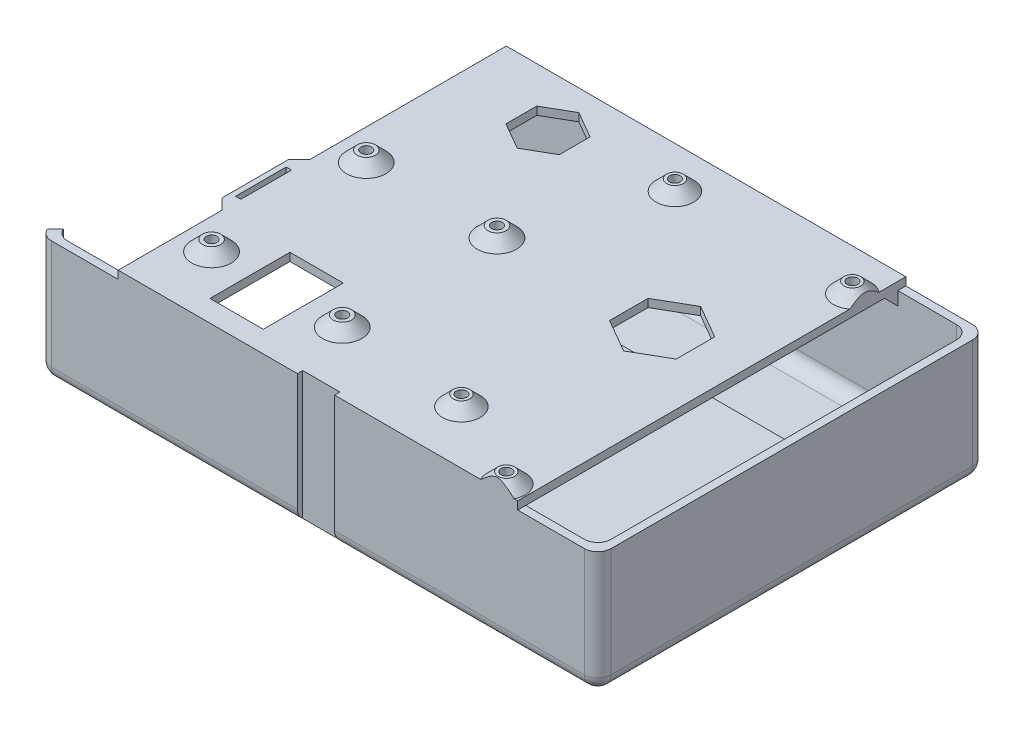
SolidWorks part; units mm, degrees
ref_plane "Front Plane" through (0, 0, 0) normal (0, 0, 1) x (1, 0, 0)
ref_plane "Top Plane" through (0, 0, 0) normal (0, 1, 0) x (1, 0, 0)
ref_plane "Right Plane" through (0, 0, 0) normal (1, 0, 0) x (0, 0, -1)
sketch "Sketch1" plane through (0, 0, 0) normal (0, 1, 0) x (1, 0, 0)
  line L1 (103.0685, -102.5392) -> (-106.7013, -102.5392)
  line L2 (103.0685, -102.5392) -> (103.0685, 42.9596)
  line L3 (103.0685, 42.9596) -> (-106.7013, 42.9596)
  line L4 (-106.7013, -102.5392) -> (-106.7013, 42.9596)
  line L6 (3.4026, -104.0392) -> (-8.5354, -104.0392) construction
  line L7 (-108.2013, -100.8421) -> (-108.2013, 38.9914) construction
  point P0 (0, 0)
  dimension "D1" = 1.5
  dimension "D2" = 1.5
extrude "Boss-Extrude1" add sketch "Sketch1" along normal blind 3
sketch "Sketch2" plane through (0, 3, 0) normal (0, 1, 0) x (1, 0, 0)
  line L4 (-106.7013, 42.9596) -> (-106.7013, -102.5392)
  line L5 (-106.7013, -102.5392) -> (103.0685, -102.5392)
  line L6 (103.0685, -102.5392) -> (103.0685, 42.9596)
  line L7 (103.0685, 42.9596) -> (-106.7013, 42.9596)
  line L8 (-106.7013, 42.9596) -> (-106.7013, -102.5392)
  line L9 (-106.7013, -102.5392) -> (103.0685, -102.5392)
  line L10 (103.0685, -102.5392) -> (103.0685, 42.9596)
  line L11 (103.0685, 42.9596) -> (-106.7013, 42.9596)
  line L16 (-103.7013, 39.9596) -> (-103.7013, -99.5392)
  line L17 (-103.7013, -99.5392) -> (100.0685, -99.5392)
  line L18 (100.0685, -99.5392) -> (100.0685, 39.9596)
  line L19 (100.0685, 39.9596) -> (-103.7013, 39.9596)
  line L20 (-103.7013, 39.9596) -> (-103.7013, -99.5392)
  line L21 (-103.7013, -99.5392) -> (100.0685, -99.5392)
  line L22 (100.0685, -99.5392) -> (100.0685, 39.9596)
  line L23 (100.0685, 39.9596) -> (-103.7013, 39.9596)
  dimension "D1" = 0
  dimension "D2" = 3
extrude "Boss-Extrude2" add sketch "Sketch2" along normal offset from surface (43 mm away) 20 offset beyond the face yes
sketch "Sketch3" plane through (-103.7013, 0, 0) normal (1, 0, 0) x (0, 0, -1)
  line L0 (39.9596, 46) -> (-99.5392, 46) construction
  line L1 (34.2109, 46) -> (-94.2682, 46)
  line L2 (34.2109, 46) -> (34.2109, 3)
  line L3 (34.2109, 3) -> (-94.2682, 3)
  line L4 (-94.2682, 46) -> (-94.2682, 3)
  line L5 (39.9596, 3) -> (-99.5392, 3) construction
extrude "Cut-Extrude1" cut sketch "Sketch3" against normal up to next
fillet "Fillet1" radius 5 8 edges at (100.0685, 24.5, 99.5392) (100.0685, 24.5, -39.9596) (-103.7013, 24.5, -39.9596) (-103.7013, 24.5, 99.5392) (103.0685, 23, -42.9596) (-106.7013, 23, -42.9596) (103.0685, 23, 102.5392) (-106.7013, 23, 102.5392)
fillet "Fillet2" radius 5 17 edges at (-103.7013, 3, 94.4037) (-102.2369, 3, 98.0748) (-1.8164, 3, 99.5392) (98.604, 3, 98.0748) (100.0685, 3, 29.7898) (98.604, 3, -38.4951) (-103.7013, 3, -34.5852) (-102.2369, 3, -38.4951) (-105.2369, 0, 101.0748) (-106.7013, 0, 29.7898) (-105.2369, 0, -41.4951) (-1.8164, 0, -42.9596) (101.604, 0, -41.4951) (103.0685, 0, 29.7898) (101.604, 0, 101.0748) (-1.8164, 3, -39.9596) (-1.8164, 0, 102.5392)
sketch "Sketch4" plane through (0, 46, 0) normal (0, 1, 0) x (1, 0, 0)
  line L0 (-101.7013, -102.5392) -> (98.0685, -102.5392) construction
  line L1 (-76.7013, -102.5392) -> (73.0685, -102.5392)
  line L2 (-76.7013, -102.5392) -> (-76.7013, 42.9596)
  line L3 (-76.7013, 42.9596) -> (73.0685, 42.9596)
  line L4 (73.0685, -102.5392) -> (73.0685, 42.9596)
  line L6 (98.0685, 42.9596) -> (-101.7013, 42.9596) construction
  line L7 (103.0685, -97.5392) -> (103.0685, 37.9596) construction
  line L8 (-106.7013, -94.2682) -> (-106.7013, -97.5392) construction
  dimension "D1" = 30
  dimension "D2" = 30
extrude "Boss-Extrude3" add sketch "Sketch4" along normal blind 3
sketch "Sketch6" plane through (0, 49, 0) normal (0, 1, 0) x (1, 0, 0)
  circle A0 centre (-16.2013, -79.0392) radius 1.4 construction
  circle A1 centre (-65.2013, -79.0392) radius 1.4 construction
  circle A2 centre (-16.2013, -21.0392) radius 1.4 construction
  circle A3 centre (-65.2013, -21.0392) radius 1.4 construction
  circle A4 centre (-16.2013, -79.0392) radius 1.4 construction
  circle A5 centre (-65.2013, -79.0392) radius 1.4 construction
  circle A6 centre (-16.2013, -21.0392) radius 1.4 construction
  circle A7 centre (-65.2013, -21.0392) radius 1.4 construction
  circle A8 centre (-65.2013, -21.0392) radius 3.4
  circle A9 centre (-65.2013, -79.0392) radius 3.4
  circle A10 centre (-16.2013, -21.0392) radius 3.4
  circle A11 centre (-16.2013, -79.0392) radius 3.4
  circle A12 centre (-65.2013, -21.0392) radius 1.1
  circle A13 centre (-16.2013, -21.0392) radius 1.1
  circle A14 centre (-65.2013, -79.0392) radius 1.1
  circle A15 centre (-16.2013, -79.0392) radius 1.1
  dimension "D2" = 2.2
  dimension "D3" = 2.2
  dimension "D4" = 2.2
  dimension "D5" = 2.2
  dimension "D1" = 2
extrude "Boss-Extrude4" add sketch "Sketch6" along normal up to surface (4 mm away)
sketch "Sketch7" plane through (0, 0, 0) normal (0, 1, 0) x (1, 0, 0)
  line L0 (-109.4507, 42.9596) -> (-106.8257, 40.3346)
  line L5 (-66.7013, 0.2102) -> (-66.7013, -59.7898)
  line L6 (-66.7013, -59.7898) -> (-99.0763, -92.1648)
  line L7 (-109.4507, -102.5392) -> (-109.4507, 42.9596)
  line L8 (-76.7013, 42.9596) -> (-76.7013, -102.5392) construction
  line L9 (-66.7013, -59.7898) -> (-66.7013, -102.5392) construction
  line L10 (-66.7013, -102.5392) -> (-109.4507, -102.5392) construction
  line L11 (-98.8263, 32.3352) -> (-66.7013, 0.2102)
  line L12 (-66.7013, 0.2102) -> (-66.7013, 42.9596) construction
  line L13 (-66.7013, 42.9596) -> (-109.4507, 42.9596) construction
  line L14 (-106.8257, 40.3346) -> (-98.8263, 32.3352)
  line L15 (-76.7013, 42.9596) -> (-101.7013, 42.9596) construction
  line L16 (-101.7013, -102.5392) -> (-76.7013, -102.5392) construction
  line L22 (-99.0763, -92.1648) -> (-107.0757, -100.1642)
  line L23 (-107.0757, -100.1642) -> (-109.4507, -102.5392)
  dimension "D1" = 45
  dimension "D2" = 45
  dimension "D3" = 10
  dimension "D4" = 60
sketch "Sketch8" plane through (0, 49, 0) normal (0, 1, 0) x (1, 0, 0)
  circle A0 centre (68.5185, 27.4596) radius 1.95 construction
  circle A1 centre (2.0185, 27.4596) radius 1.95 construction
  circle A2 centre (68.5185, 27.4596) radius 1.95 construction
  circle A3 centre (2.0185, 27.4596) radius 1.95 construction
  circle A4 centre (2.0185, 27.4596) radius 1.1
  circle A5 centre (68.5185, 27.4596) radius 1.1
  circle A6 centre (2.0185, 27.4596) radius 3.1
  circle A7 centre (68.5185, 27.4596) radius 3.1
  dimension "D1" = 2.2
  dimension "D2" = 2.2
  dimension "D3" = 2
extrude "Boss-Extrude5" add sketch "Sketch8" along normal up to surface (4 mm away)
sketch "Sketch9" plane through (0, 49, 0) normal (0, 1, 0) x (1, 0, 0)
  circle A0 centre (31.8985, -82.4792) radius 1.5 construction
  circle A1 centre (65.4585, -99.1992) radius 1.5 construction
  circle A2 centre (31.8985, -82.4792) radius 1.5 construction
  circle A3 centre (65.4585, -99.1992) radius 1.5 construction
  circle A4 centre (31.8985, -82.4792) radius 1.1
  circle A5 centre (65.4585, -99.1992) radius 1.1
  circle A6 centre (31.8985, -82.4792) radius 3.1
  circle A7 centre (65.4585, -99.1992) radius 3.1
  dimension "D1" = 2.2
  dimension "D2" = 2.2
  dimension "D3" = 2
  dimension "D4" = 2
extrude "Boss-Extrude6" add sketch "Sketch9" along normal up to surface (4 mm away) contours A7 A5 | A6 A4 region at (28.8862, 49, 82.4792) region at (62.4462, 49, 99.1992)
extrude "Cut-Extrude3" cut sketch "Sketch7" along normal up to surface (46 mm away) up to face at (-1.8164, 46, 29.7898)
extrude "Cut-Extrude4" cut sketch "Sketch6<3>" against normal up to next contours A14 | A12 | A13 | A15 region at (-65.2013, 49, 21.0392) region at (-16.2013, 49, 21.0392) region at (-65.2013, 49, 79.0392) region at (-16.2013, 49, 79.0392)
sketch "Sketch6<3>" plane through (0, 49, 0) normal (0, 1, 0) x (1, 0, 0) same geometry as "Sketch6"
extrude "Cut-Extrude5" cut sketch "Sketch8<2>" against normal up to next contours A4 | A5 region at (2.0185, 49, -27.4596) region at (68.5185, 49, -27.4596)
sketch "Sketch8<2>" plane through (0, 49, 0) normal (0, 1, 0) x (1, 0, 0) same geometry as "Sketch8"
extrude "Cut-Extrude6" cut sketch "Sketch9<2>" against normal up to surface (3 mm away) contours A4 | A5 region at (31.8985, 49, 82.4792) region at (65.4585, 49, 99.1992) up to face at (2.0185, 46, -28.5596)
sketch "Sketch9<2>" plane through (0, 49, 0) normal (0, 1, 0) x (1, 0, 0) same geometry as "Sketch9"
chamfer "Chamfer1" distance 4 angle 45 8 edges at (-65.2013, 49, 17.6392) (-65.2013, 49, 75.6392) (-16.2013, 49, 17.6392) (-16.2013, 49, 75.6392) (65.4585, 49, 96.0992) (31.8985, 49, 79.3792) (68.5185, 49, -30.5596) (2.0185, 49, -30.5596)
sketch "Sketch10" plane through (0, 0, 0) normal (0, 1, 0) x (1, 0, 0)
  line L0 (-9.5354, -102.5392) -> (-9.5354, -100.5392)
  line L1 (-76.7013, -102.5392) -> (59.1932, -102.5392) construction
  line L2 (-9.5354, -100.5392) -> (4.4026, -100.5392)
  line L3 (4.4026, -100.5392) -> (4.4026, -102.5392)
  line L4 (4.4026, -102.5392) -> (-9.5354, -102.5392)
  line L5 (-8.5354, -104.0392) -> (-8.5354, -105.7188) construction
  dimension "D1" = 1
  dimension "D2" = 1
  dimension "D3" = 2
extrude "Cut-Extrude7" cut sketch "Sketch10" along normal up to surface (49 mm away) up to face at (-65.2013, 49, 13.6392)
sketch "Sketch11" plane through (0, 49, 0) normal (0, 1, 0) x (1, 0, 0)
  line L0 (-76.7013, -35.5392) -> (-80.7013, -35.5392)
  line L1 (-76.7013, 42.9596) -> (-76.7013, -102.5392) construction
  line L2 (-80.7013, -35.5392) -> (-80.7013, -58.5392)
  line L3 (-80.7013, -58.5392) -> (-76.7013, -58.5392)
  line L4 (-76.7013, -58.5392) -> (-76.7013, -56.5392)
  line L5 (-76.7013, -56.5392) -> (-78.7013, -56.5392)
  line L6 (-78.7013, -56.5392) -> (-78.7013, -37.5392)
  line L7 (-78.7013, -37.5392) -> (-76.7013, -37.5392)
  line L8 (-76.7013, -37.5392) -> (-76.7013, -35.5392)
  line L9 (-20.7013, -82.5392) -> (-60.7013, -82.5392) construction
  dimension "D1" = 2
  dimension "D2" = 2
  dimension "D3" = 2
  dimension "D4" = 19
  dimension "D5" = 2
  dimension "D6" = 26
extrude "Boss-Extrude7" add sketch "Sketch11" against normal up to surface (3 mm away) up to face at (31.8985, 46, 81.3792)
chamfer "Chamfer2" distance 5 angle 45 2 edges at (-76.7013, 47.5, 35.5392) (-76.7013, 47.5, 58.5392)
sketch "Sketch12" plane through (100.0685, 0, 0) normal (-1, 0, 0) x (0, 0, 1)
  line L0 (14.5392, 3) -> (14.5392, 31)
  line L1 (14.5392, 31) -> (99.5392, 31)
  line L2 (99.5392, 46) -> (99.5392, 8) construction
  line L3 (94.5392, 3) -> (-34.9596, 3) construction
  line L4 (94.5392, 3) -> (14.5392, 3) construction
  line L5 (99.5392, 8) -> (99.5392, 31) construction
  line L6 (17.5392, 3) -> (17.5392, 28)
  line L7 (17.5392, 28) -> (99.5392, 28)
  line L8 (17.5392, 3) -> (14.5392, 3)
  line L9 (99.5392, 28) -> (99.5392, 31)
  arc A0 (94.5392, 3) -> (99.5392, 8) centre (94.5392, 8) ccw construction
  arc A1 (94.5392, 3) -> (99.5392, 8) centre (94.5392, 8) ccw construction
  dimension "D2" = 82
  dimension "D3" = 25
  dimension "D1" = 3
extrude "Boss-Extrude8" add sketch "Sketch12" along normal up to surface (166.7698 mm away) up to face at (-66.7013, 1.5, 29.7898)
sketch "Sketch13" plane through (0, 0, -42.9596) normal (0, 0, -1) x (-1, 0, 0)
  line L0 (76.7013, 46) -> (106.3334, 46)
  line L1 (106.3334, 46) -> (106.3334, 0)
  line L2 (106.3334, 0) -> (76.7013, 46)
extrude "Cut-Extrude8" cut sketch "Sketch13" against normal up to next
chamfer "Chamfer3" distance 5 angle 45 1 edges at (-1.8164, 46, -39.9596)
chamfer "Chamfer4" distance 1 angle 45 1 edges at (-6.1445, 46, 99.5392)
sketch "Sketch14" plane through (0, 49, 0) normal (0, 1, 0) x (1, 0, 0)
  line L0 (95.0685, -99.5392) -> (-98.7013, -99.5392) construction
  line L1 (-50.3226, -94.5392) -> (-30.3226, -94.5392)
  line L2 (-50.3226, -94.5392) -> (-50.3226, -64.5392)
  line L3 (-50.3226, -64.5392) -> (-30.3226, -64.5392)
  line L4 (-30.3226, -94.5392) -> (-30.3226, -64.5392)
  dimension "D1" = 5
  dimension "D2" = 20
  dimension "D3" = 30
extrude "Cut-Extrude9" cut sketch "Sketch14" against normal up to surface (21 mm away) up to face at (32.5677, 28, 65.9463)
chamfer "Chamfer5" distance 2 angle 45 6 edges at (100.0685, 31, 54.5392) (98.604, 31, 98.0748) (14.1836, 31, 99.5392) (100.0685, 19.5, 14.5392) (98.604, 4.4645, 14.5392) (14.1836, 3, 14.5392)
sketch "Sketch15" plane through (0, 49, 0) normal (0, 1, 0) x (1, 0, 0)
  line L7 (44.2685, -5.1537) -> (31.7685, -12.3706)
  line L8 (31.7685, -12.3706) -> (31.7685, -26.8043)
  line L9 (31.7685, -26.8043) -> (44.2685, -34.0212)
  line L10 (44.2685, -34.0212) -> (56.7685, -26.8043)
  line L11 (56.7685, -26.8043) -> (56.7685, -12.3706)
  line L12 (56.7685, -12.3706) -> (44.2685, -5.1537)
  line L14 (64.7685, 11.9596) -> (64.7685, 23.3096) construction
  line L15 (-76.7013, 34.9596) -> (73.0685, 34.9596) construction
  line L16 (-41.5128, 34.9596) -> (-51.5128, 29.1861)
  line L17 (-51.5128, 29.1861) -> (-51.5128, 17.6391)
  line L18 (-51.5128, 17.6391) -> (-41.5128, 11.8656)
  line L19 (-41.5128, 11.8656) -> (-31.5128, 17.6391)
  line L20 (-31.5128, 17.6391) -> (-31.5128, 29.1861)
  line L21 (-31.5128, 29.1861) -> (-41.5128, 34.9596)
  circle A1 centre (44.2685, -19.5874) radius 12.5 construction
  circle A2 centre (-41.5128, 23.4126) radius 10 construction
  dimension "D2" = 25
  dimension "D5" = 8
  dimension "D6" = 20
extrude "Cut-Extrude10" cut sketch "Sketch15" against normal up to next
sketch "Sketch16" plane through (0, 31, 0) normal (0, 1, 0) x (1, 0, 0)
  line L5 (-50.3226, -94.5392) -> (-66.7013, -94.5392)
  line L6 (-66.7013, -97.5392) -> (-66.7013, -14.5392) construction
  line L7 (-66.7013, -94.5392) -> (-66.7013, -28.1605)
  line L8 (-66.7013, -28.1605) -> (-30.3226, -64.5392)
  line L9 (-30.3226, -64.5392) -> (-50.3226, -64.5392)
  line L10 (-50.3226, -64.5392) -> (-50.3226, -94.5392)
  dimension "D1" = 45
extrude "Cut-Extrude11" cut sketch "Sketch16" against normal up to next
sketch "Sketch17" plane through (0, 53, 0) normal (0, 1, 0) x (1, 0, 0)
  circle A0 centre (-65.2013, -79.0392) radius 2
  circle A1 centre (-16.2013, -79.0392) radius 2
  circle A2 centre (65.4585, -99.1992) radius 2
  circle A3 centre (31.8985, -82.4792) radius 2
  circle A4 centre (-16.2013, -21.0392) radius 2
  circle A5 centre (-65.2013, -21.0392) radius 2
  circle A6 centre (2.0185, 27.4596) radius 2
  circle A7 centre (68.5185, 27.4596) radius 2
  dimension "D1" = 4
  dimension "D2" = 4
  dimension "D3" = 4
  dimension "D4" = 4
  dimension "D5" = 4
  dimension "D6" = 4
  dimension "D7" = 4
  dimension "D8" = 4
extrude "Cut-Extrude12" cut sketch "Sketch17" against normal up to surface (7 mm away) up to face at (44.2685, 46, 19.5874)
